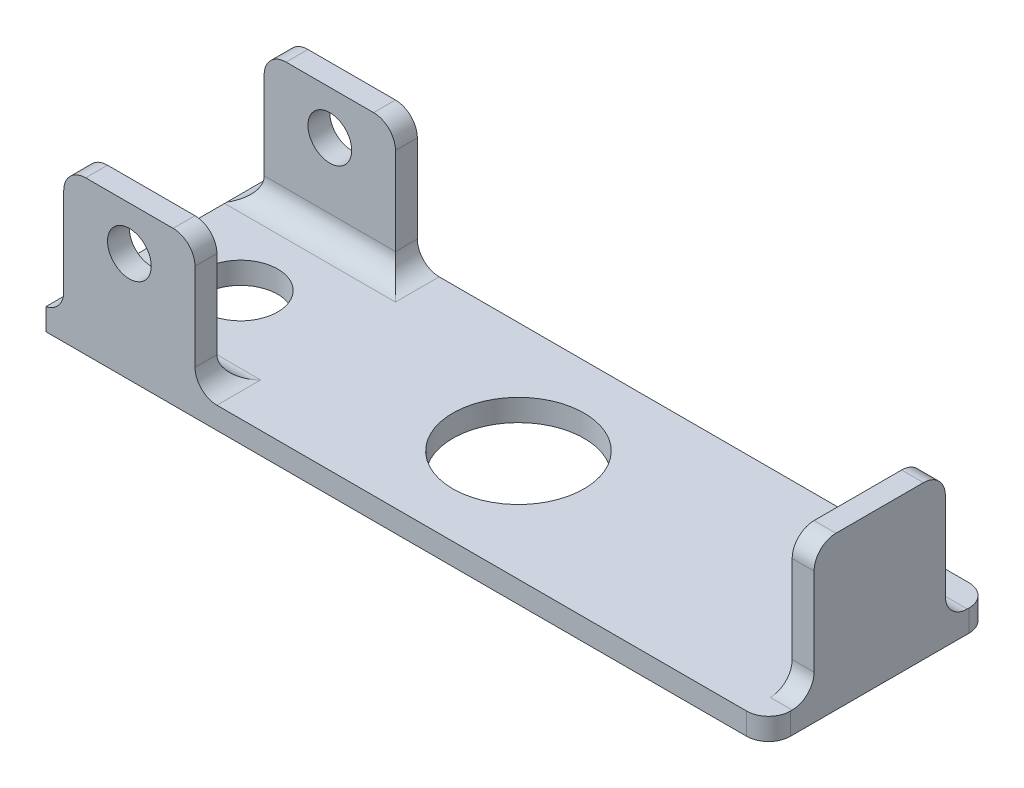
SolidWorks part; units mm, degrees
ref_plane "Front Plane" through (0, 0, 0) normal (0, 0, 1) x (1, 0, 0)
ref_plane "Top Plane" through (0, 0, 0) normal (0, 1, 0) x (1, 0, 0)
ref_plane "Right Plane" through (0, 0, 0) normal (1, 0, 0) x (0, 0, -1)
sketch "Sketch1" plane through (0, 0, 0) normal (0, 1, 0) x (1, 0, 0)
  line L1 (-16.51, -5.08) -> (16.51, -5.08)
  line L2 (-16.51, -5.08) -> (-16.51, 5.08)
  line L3 (-16.51, 5.08) -> (16.51, 5.08)
  line L4 (16.51, -5.08) -> (16.51, 5.08)
  circle A0 centre (0, 0) radius 3
  circle A1 centre (-12.7, 0) radius 1.7
  point P8 (-16.51, 0)
  dimension "D1" = 6
  dimension "D2" = 3.4
  dimension "D3" = 12.7
  dimension "D4" = 16.51
  dimension "D5" = 5.08
  dimension "D6" = 3.81
extrude "Boss-Extrude1" add sketch "Sketch1" along normal blind 1
sketch "Sketch2" plane through (0, 1, 0) normal (0, 1, 0) x (1, 0, 0)
  line L0 (-12.7, 0) -> (-12.7, 2.3333) construction
  line L1 (-15.7, 5.08) -> (-9.7, 5.08)
  line L2 (-15.7, 5.08) -> (-15.7, 4.08)
  line L3 (-15.7, 4.08) -> (-9.7, 4.08)
  line L4 (-9.7, 5.08) -> (-9.7, 4.08)
  line L5 (-15.7, -5.08) -> (-9.7, -5.08)
  line L6 (-15.7, -5.08) -> (-15.7, -4.08)
  line L7 (-15.7, -4.08) -> (-9.7, -4.08)
  line L8 (-9.7, -5.08) -> (-9.7, -4.08)
  line L9 (-16.51, -5.08) -> (16.51, -5.08) construction
  line L10 (16.51, 5.08) -> (-16.51, 5.08) construction
  line L11 (16.51, -5.08) -> (16.51, 5.08) construction
  line L12 (16.51, 3) -> (15.51, 3)
  line L13 (16.51, 3) -> (16.51, -3)
  line L14 (16.51, -3) -> (15.51, -3)
  line L15 (15.51, 3) -> (15.51, -3)
  point P10 (-12.7, 4.08)
  point P22 (16.51, 0)
  dimension "D1" = 6
  dimension "D2" = 1
  dimension "D3" = 1
  dimension "D4" = 1
  dimension "D5" = 6
extrude "Boss-Extrude2" add sketch "Sketch2" along normal blind 6
sketch "Sketch3" plane through (0, 0, 5.08) normal (0, 0, 1) x (1, 0, 0)
  line L0 (-15.7, 7) -> (-9.7, 7) construction
  circle A0 centre (-12.7, 5) radius 1
  point P5 (-12.7, 7)
  dimension "D2" = 2
  dimension "D1" = 2
extrude "Cut-Extrude1" cut sketch "Sketch3" against normal through all
fillet "Fillet1" radius 1 16 edges at (-15.7, 7, 4.58) (-15.7, 1, 4.58) (-15.7, 1, -4.58) (-15.7, 7, -4.58) (-9.7, 7, 4.58) (-9.7, 1, 4.58) (-9.7, 7, -4.58) (-9.7, 1, -4.58) (16.51, 0.5, -5.08) (16.01, 1, -3) (16.01, 7, -3) (16.01, 7, 3) (16.01, 1, 3) (16.51, 0.5, 5.08) (-12.7, 1, 4.08) (-12.7, 1, -4.08)
sketch "Sketch4" plane through (0, 0, 0) normal (0, 0, 1) x (1, 0, 0)
  line L1 (15.51, 6) -> (15.51, 2) construction
  line L2 (14.51, 5) -> (15.51, 6)
  line L3 (15.51, 6) -> (15.51, 4.5)
  line L4 (16.51, 6) -> (15.51, 6) construction
  line L5 (14.51, 5) -> (14.51, 4.5)
  line L6 (14.51, 4.5) -> (15.51, 4.5)
  dimension "D1" = 1.5
  dimension "D2" = 1
  dimension "D3" = 0.5
extrude "Boss-Extrude3" add sketch "Sketch4" along normal blind 1 and the other way blind 1
